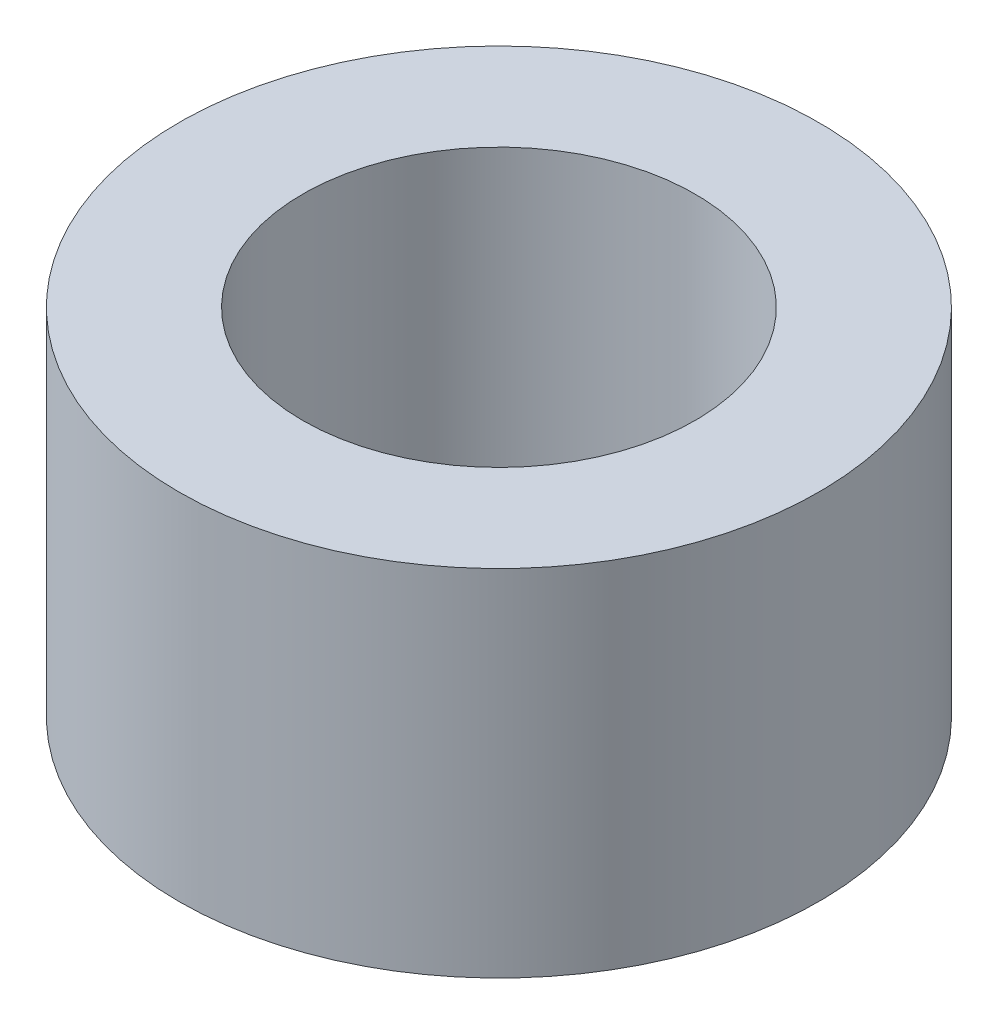
SolidWorks part; units mm, degrees
ref_plane "Front Plane" through (0, 0, 0) normal (0, 0, 1) x (1, 0, 0)
ref_plane "Top Plane" through (0, 0, 0) normal (0, 1, 0) x (1, 0, 0)
ref_plane "Right Plane" through (0, 0, 0) normal (1, 0, 0) x (0, 0, -1)
sketch "Sketch1" plane through (0, 0, 0) normal (0, 1, 0) x (1, 0, 0)
  circle A0 centre (0, 0) radius 64.9649
extrude "Boss-Extrude1" add sketch "Sketch1" along normal blind 72
sketch "Sketch2" plane through (0, 72, 0) normal (0, 1, 0) x (1, 0, 0)
  circle A0 centre (0, 0) radius 39.8269
extrude "Cut-Extrude1" cut sketch "Sketch2" against normal blind 72
